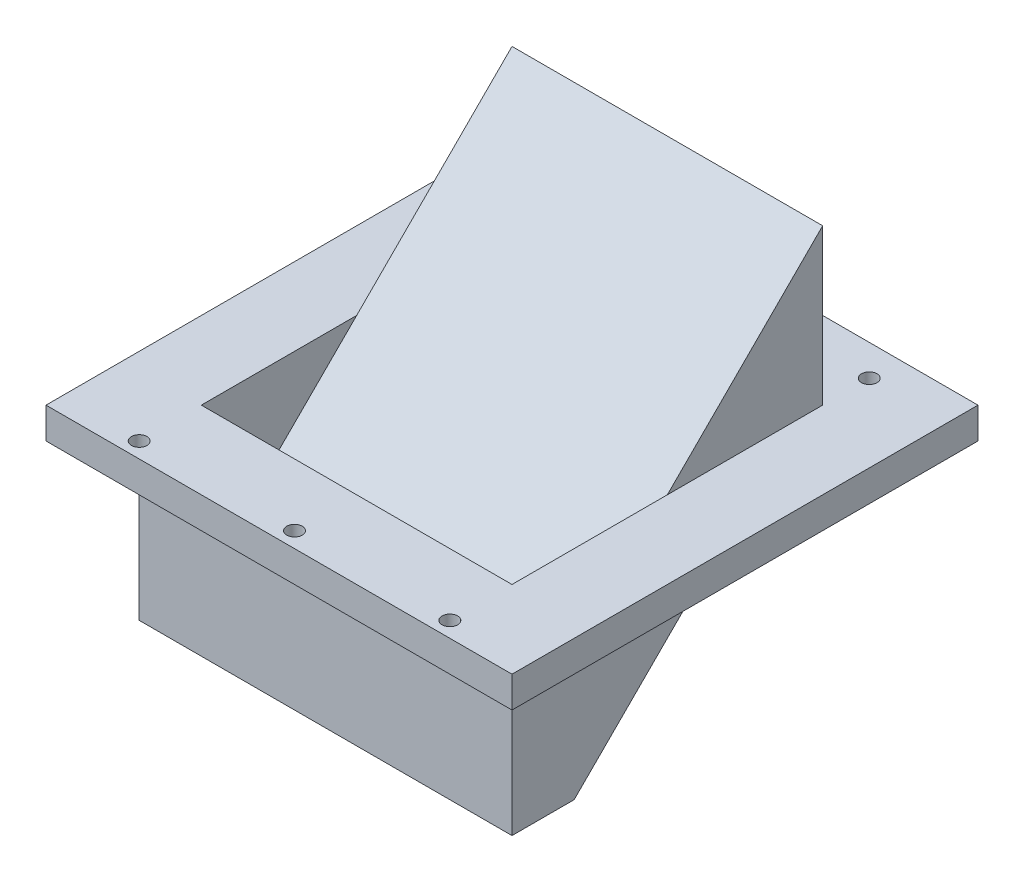
SolidWorks part; units mm, degrees
ref_plane "Front Plane" through (0, 0, 0) normal (0, 0, 1) x (1, 0, 0)
ref_plane "Top Plane" through (0, 0, 0) normal (0, 1, 0) x (1, 0, 0)
ref_plane "Right Plane" through (0, 0, 0) normal (1, 0, 0) x (0, 0, -1)
sketch "Sketch1" plane through (0, 0, 0) normal (0, 1, 0) x (1, 0, 0)
  line L1 (0, 0) -> (150, 0)
  line L2 (0, 0) -> (0, 150)
  line L3 (0, 150) -> (150, 150)
  line L4 (150, 0) -> (150, 150)
  dimension "D1" = 150
  dimension "D2" = 150
extrude "Boss-Extrude1" add sketch "Sketch1" along normal blind 10
sketch "Sketch3" plane through (0, 10, 0) normal (0, 1, 0) x (1, 0, 0)
  line L0 (150, 150) -> (0, 150) construction
  line L1 (25, 25) -> (125, 25)
  line L2 (25, 25) -> (25, 125)
  line L3 (25, 125) -> (125, 125)
  line L4 (125, 25) -> (125, 125)
  line L5 (0, -5.5) -> (0, 5.5) construction
  line L6 (25, 75) -> (125, 75)
  dimension "D1" = 100
  dimension "D2" = 100
  dimension "D3" = 25
  dimension "D4" = 25
extrude "Boss-Extrude2" add sketch "Sketch3" along normal blind 50 contours L2 L6 L4 L3 region at (75, 10, -100)
sketch "Sketch4" plane through (25, 0, 0) normal (-1, 0, 0) x (0, 0, 1)
  line L0 (-125, 60) -> (-75, 10)
  line L1 (-75, 60) -> (-125, 60) construction
  line L2 (-125, 60) -> (-125, 10) construction
  line L3 (-75, 10) -> (-125, 10) construction
  line L4 (-75, 10) -> (-75, 60)
  line L5 (-75, 60) -> (-125, 60)
extrude "Cut-Extrude1" cut sketch "Sketch4" against normal through all
sketch "Sketch5" plane through (0, 10, 0) normal (0, 1, 0) x (1, 0, 0)
  line L0 (25, 75) -> (25, 25)
  line L1 (25, 25) -> (125, 25)
  line L2 (125, 25) -> (125, 75)
  line L3 (125, 75) -> (25, 75)
  dimension "D1" = 100
  dimension "D2" = 50
extrude "Cut-Extrude2" cut sketch "Sketch5" against normal through all
sketch "Sketch6" plane through (25, 0, 0) normal (1, 0, 0) x (0, 0, -1)
  line L0 (75, 10) -> (25, 10)
  line L1 (25, 10) -> (25, -40)
  line L2 (25, -40) -> (75, 10)
  line L3 (25, 0) -> (65, 0)
  line L4 (75, 0) -> (25, 0) construction
  line L5 (65, 0) -> (75, 0)
  line L6 (75, 0) -> (75, 10)
  line M3 (25, 0) -> (75, 0)
  line M4 (75, 0) -> (75, 10)
  dimension "D1" = 50
sketch "Sketch7" plane through (0, 0, 0) normal (0, -1, 0) x (1, 0, 0)
  line L0 (125, -75) -> (25, -75) construction
  line L1 (135, -85) -> (15, -85)
  line L2 (135, -85) -> (135, -15)
  line L3 (135, -15) -> (15, -15)
  line L4 (15, -85) -> (15, -15)
  line L6 (25, -25) -> (125, -25) construction
  line L7 (125, -25) -> (125, -75) construction
  line L8 (25, -75) -> (25, -25) construction
  dimension "D1" = 10
  dimension "D2" = 10
  dimension "D3" = 10
  dimension "D4" = 10
extrude "Boss-Extrude6" add sketch "Sketch7" along normal blind 50
extrude "Boss-Extrude7" add sketch "Sketch6" along normal blind 100 contours L2 M3 M4 region at (25, 3.3333, -71.6667)
sketch "Sketch9" plane through (0, 0, 0) normal (0, 1, 0) x (1, 0, 0)
  line L1 (25, 65) -> (125, 65)
  line L2 (25, 65) -> (25, 25)
  line L3 (25, 25) -> (125, 25)
  line L4 (125, 65) -> (125, 25)
extrude "Cut-Extrude4" cut sketch "Sketch9" against normal blind 40
sketch "Sketch10" plane through (25, 0, 0) normal (1, 0, 0) x (0, 0, -1)
  line L0 (65, 0) -> (25, -40)
  line L1 (25, -40) -> (65, -40)
  line L2 (65, -40) -> (65, 0)
extrude "Boss-Extrude8" add sketch "Sketch10" along normal blind 100
sketch "Sketch11" plane through (135, 0, 0) normal (1, 0, 0) x (0, 0, -1)
  line L0 (85, 0) -> (85, -50)
  line L1 (85, -50) -> (35, -50)
  line L2 (85, -50) -> (15, -50) construction
  line L3 (35, -50) -> (85, 0)
  dimension "D1" = 50
extrude "Cut-Extrude5" cut sketch "Sketch11" against normal through all
shell "Shell1" thickness 10 removed face at (75, 35, -125)
sketch "Sketch12" plane through (0, 0, 0) normal (0, -1, 0) x (1, 0, 0)
  line L0 (150, -150) -> (0, -150) construction
  line L1 (150, 0) -> (150, -150) construction
  line L2 (0, -150) -> (0, 0) construction
  line L3 (0, 0) -> (150, 0) construction
  line L4 (60.5, 0) -> (-60.5, 0) construction
  circle A0 centre (125, -140) radius 2.5
  circle A1 centre (75, -140) radius 2.5
  circle A2 centre (25, -140) radius 2.5
  circle A3 centre (125, -5) radius 2.5
  circle A4 centre (75, -5) radius 2.5
  circle A5 centre (25, -5) radius 2.5
  dimension "D2" = 5
  dimension "D4" = 5
  dimension "D7" = 5
  dimension "D10" = 5
  dimension "D11" = 5
  dimension "D12" = 5
  dimension "D1" = 10
  dimension "D3" = 25
  dimension "D5" = 25
  dimension "D6" = 10
  dimension "D8" = 75
  dimension "D9" = 10
  dimension "D13" = 25
  dimension "D14" = 5
  dimension "D15" = 5
  dimension "D16" = 5
extrude "Cut-Extrude6" cut sketch "Sketch12" against normal through all
